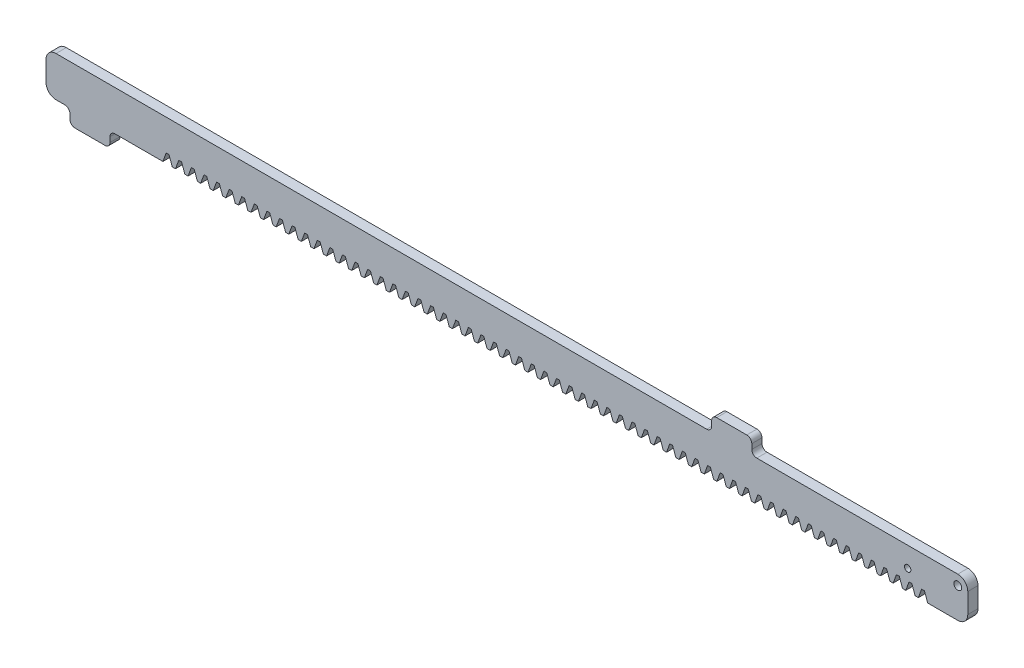
SolidWorks part; units mm, degrees
material "PC High Viscosity"
ref_plane "Front Plane" through (0, 0, 0) normal (0, 0, 1) x (1, 0, 0)
ref_plane "Top Plane" through (0, 0, 0) normal (0, 1, 0) x (1, 0, 0)
ref_plane "Right Plane" through (0, 0, 0) normal (1, 0, 0) x (0, 0, -1)
sketch "Sketch1" plane through (0, 0, 0) normal (0, 0, 1) x (1, 0, 0)
  line L1 (0, 0) -> (15.1307, 0)
  line L2 (0, 0) -> (0, 25.4)
  line L3 (0, 25.4) -> (40.5308, 25.4)
  line L4 (584.2, 0) -> (584.2, 25.4)
  line L7 (533.4, 25.4) -> (584.2, 25.4)
  line L8 (40.5308, 25.4) -> (421.9033, 25.4)
  line L9 (40.5307, 0) -> (584.2, 0)
  line L11 (584.2, 22.7162) -> (577.85, 26.3823) construction
  line L12 (577.85, 26.3823) -> (571.5, 22.7162) construction
  line L13 (571.5, 22.7162) -> (571.5, 15.3838) construction
  line L14 (571.5, 15.3838) -> (577.85, 11.7177) construction
  line L15 (577.85, 11.7177) -> (584.2, 15.3838) construction
  line L16 (584.2, 15.3838) -> (584.2, 22.7162) construction
  line L19 (590.55, 0) -> (590.55, 10.0162) construction
  line L20 (590.55, 10.0162) -> (76.2, 10.0162) construction
  line L21 (76.2, 10.0162) -> (76.2, 0) construction
  line L22 (447.3033, 25.4) -> (533.4, 25.4)
  line L26 (15.1307, 0) -> (15.1307, -9.525)
  line L27 (15.1307, -9.525) -> (40.5307, -9.525)
  line L28 (40.5307, -9.525) -> (40.5307, 0)
  line L29 (421.9033, 25.4) -> (421.9033, 34.925)
  line L30 (421.9033, 34.925) -> (447.3033, 34.925)
  line L31 (447.3033, 34.925) -> (447.3033, 25.4)
  circle A0 centre (577.85, 19.05) radius 2.4892
  circle A1 centre (577.85, 19.05) radius 6.35 construction
  dimension "D5" = 4.9784
  dimension "D6" = 40.5307
  dimension "D7" = 12.7
  dimension "D1" = 584.2
  dimension "D2" = 25.4
  dimension "D3" = 421.9033
  dimension "D4" = 9.525
  dimension "D8" = 25.4
  dimension "D9" = 25.4
extrude "Boss-Extrude1" add sketch "Sketch1" along normal blind 6.477 contours L3 | L1 L4 L3 L2 A0 | L1 region at (289.8115, 12.6919, 0)
fillet "Fillet2" radius 6.35 4 edges at (0, 0, 3.2385) (0, 25.4, 3.2385) (584.2, 25.4, 3.2385) (584.2, 0, 3.2385)
sketch "Sketch2" plane through (0, 0, 6.477) normal (0, 0, 1) x (1, 0, 0)
  line L0 (558.8, 0) -> (43.7057, 0)
  line L1 (43.7057, 0) -> (43.7057, 5.715)
  line L2 (43.7057, 5.715) -> (558.8, 5.715)
  line L3 (558.8, 5.715) -> (558.8, 0)
  line L5 (557.8755, 2.54) -> (549.711, 2.54) construction
  line L6 (558.8, 0) -> (556.7199, 5.715)
  line L7 (142.1307, 0) -> (654.4688, 0) construction
  line L8 (552.8688, 0) -> (558.8, 0)
  line L10 (556.7199, 5.715) -> (554.9488, 5.715)
  line L11 (558.8, 0) -> (552.8688, 0)
  line L12 (552.8688, 0) -> (554.9488, 5.715)
  line L13 (554.9488, 5.715) -> (556.7199, 5.715)
  line L14 (558.8, 0) -> (552.8688, 0)
  line L15 (554.9488, 5.715) -> (556.7199, 5.715)
  line L16 (558.8, 0) -> (552.8688, 0)
  line L17 (552.8688, 0) -> (558.8, 0)
  line L19 (556.7199, 5.715) -> (554.9488, 5.715) construction
  line L20 (552.8688, 0) -> (558.8, 0) construction
  line L21 (0, 0) -> (15.1307, 0) construction
  line L22 (584.2, 0) -> (584.2, 25.4) construction
  line L23 (40.5307, 0) -> (584.2, 0) construction
  point P8 (553.7932, 2.54)
  point P16 (557.8755, 2.54)
  dimension "D1" = 70
  dimension "D2" = 2.54
  dimension "D3" = 3.175
  dimension "D4" = 70
  dimension "D5" = 1.7711
  dimension "D6" = 25.4
extrude "Cut-Extrude1" cut sketch "Sketch2" against normal through all contours L12 L0 L8 L6 L2 region at (555.8344, 2.343, 6.477)
pattern_linear "LPattern1" count 61 spacing 7.9796 along (-1, 0, 0) of "Cut-Extrude1"
sketch "Sketch3" plane through (0, 0, 6.477) normal (0, 0, 1) x (1, 0, 0)
  line L2 (533.4, 25.4) -> (584.2, 25.4) construction
  line L3 (584.2, 0) -> (584.2, 25.4) construction
  circle A0 centre (546.1, 12.7) radius 2.0193
  dimension "D2" = 4.0386
  dimension "D1" = 12.7
  dimension "D3" = 38.1
extrude "Cut-Extrude2" cut sketch "Sketch3" against normal through all
fillet "Fillet3" radius 3.175 8 edges at (421.9033, 25.4, 3.2385) (421.9033, 34.925, 3.2385) (447.3033, 34.925, 3.2385) (447.3033, 25.4, 3.2385) (40.5307, -9.525, 3.2385) (40.5307, 0, 3.2385) (15.1307, -9.525, 3.2385) (15.1307, 0, 3.2385)
